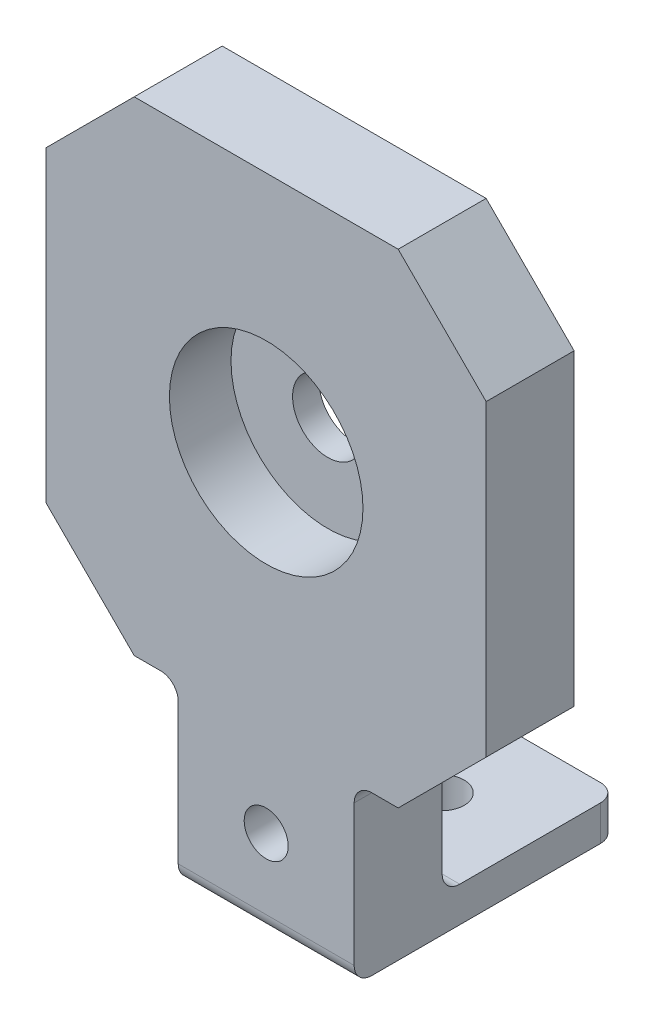
SolidWorks part; units mm, degrees
material "PLA"
ref_plane "Piano frontale" through (0, 0, 0) normal (0, 0, 1) x (1, 0, 0)
ref_plane "Piano superiore" through (0, 0, 0) normal (0, 1, 0) x (1, 0, 0)
ref_plane "Piano destro" through (0, 0, 0) normal (1, 0, 0) x (0, 0, -1)
sketch "Schizzo1" plane through (0, 0, 0) normal (0, 0, 1) x (1, 0, 0)
  line L28 (-25, 20) -> (-10, 20)
  line L37 (-25, 20) -> (-25, 75)
  line L38 (-25, 75) -> (25, 75)
  line L39 (25, 20) -> (25, 75)
  line L40 (-10, 0) -> (10, 0)
  line L41 (-10, 0) -> (-10, 20)
  line L42 (10, 0) -> (10, 20)
  line L43 (10, 20) -> (25, 20)
  circle A5 centre (0, 47.5) radius 4
  point P0 (0, 0)
  point P4 (0, 75)
  dimension "D2" = 15
  dimension "D7" = 27.5
  dimension "D6" = 8
  dimension "D1" = 15
  dimension "D4" = 50
  dimension "D3" = 55
  dimension "D5" = 20
extrude "Estrusione-Estrusione1" add sketch "Schizzo1" along normal blind 10
chamfer "Smusso1" distance 10 angle 45 4 edges at (-25, 75, 5) (-25, 20, 5) (25, 20, 5) (25, 75, 5)
sketch "Schizzo3" plane through (0, 0, 10) normal (0, 0, 1) x (1, 0, 0)
  circle A0 centre (0, 47.5) radius 11
  dimension "D1" = 22
extrude "Taglio-Estrusione1" cut sketch "Schizzo3" against normal blind 7
sketch "Schizzo4" plane through (0, 0, 0) normal (0, 0, -1) x (-1, 0, 0)
  line L0 (10, 20) -> (10, 0) construction
  line L1 (-10, 0) -> (10, 0)
  line L2 (-10, 0) -> (-10, 4)
  line L3 (-10, 4) -> (10, 4)
  line L4 (10, 0) -> (10, 4)
  dimension "D1" = 4
extrude "Estrusione-Estrusione2" add sketch "Schizzo4" along normal blind 20
fillet "Raccordo1" radius 2 6 edges at (0, 0, 10) (0, 4, 0) (-10, 20, 5) (10, 20, 5) (-10, 2, -20) (10, 2, -20)
sketch "Schizzo5" plane through (0, 4, 0) normal (0, 1, 0) x (1, 0, 0)
  line L0 (10, 0) -> (-10, 0) construction
  circle A0 centre (0, 10) radius 2.5
  dimension "D1" = 5
  dimension "D2" = 10
extrude "Taglio-Estrusione2" cut sketch "Schizzo5" against normal blind 20
sketch "Schizzo6" plane through (0, 0, 0) normal (0, 0, -1) x (-1, 0, 0)
  line L0 (-8, 0) -> (8, 0) construction
  circle A0 centre (0, 10) radius 2.5
  dimension "D1" = 5
  dimension "D2" = 10
extrude "Taglio-Estrusione3" cut sketch "Schizzo6" against normal through all
